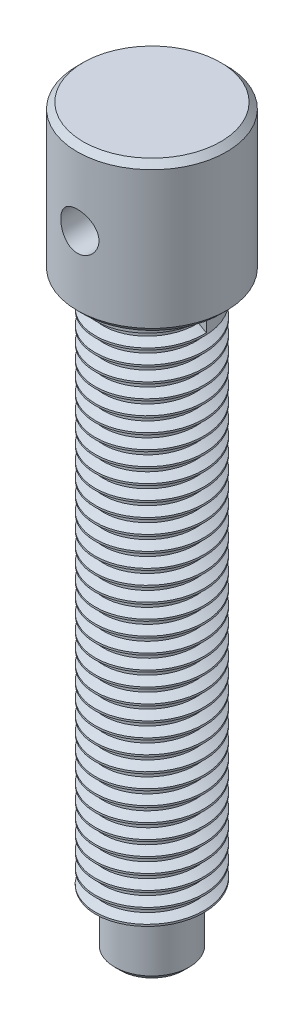
SolidWorks part; units mm, degrees
ref_plane "Front Plane" through (0, 0, 0) normal (0, 0, 1) x (1, 0, 0)
ref_plane "Top Plane" through (0, 0, 0) normal (0, 1, 0) x (1, 0, 0)
ref_plane "Right Plane" through (0, 0, 0) normal (1, 0, 0) x (0, 0, -1)
sketch "Sketch1" plane through (0, 0, 0) normal (0, 1, 0) x (1, 0, 0)
  circle A0 centre (0, 0) radius 6.35
  dimension "D1" = 12.7
extrude "Boss-Extrude1" add sketch "Sketch1" against normal blind 12.7
sketch "Sketch2" plane through (0, -12.7, 0) normal (0, -1, 0) x (1, 0, 0)
  circle A0 centre (0, 0) radius 4.625
  dimension "D1" = 9.25
extrude "Boss-Extrude2" add sketch "Sketch2" along normal blind 45
sketch "Sketch3" plane through (0, -57.7, 0) normal (0, -1, 0) x (1, 0, 0)
  circle A0 centre (0, 0) radius 3.175
  dimension "D1" = 6.35
extrude "Boss-Extrude3" add sketch "Sketch3" along normal blind 5
chamfer "Chamfer1" distance 0.5 angle 45 3 edges at (0, 0, 6.35) (0, -12.7, 6.35) (0, -62.7, -3.175)
thread "Thread1" pitch 1.25 method cut profile "Thread Profile1" start angle 0, offset 2, length 45, pitch 1.25, diameter 9.25
ref_plane "Plane1" through (4.625, -59.7, 0) normal (0, 0, 1) x (1, 0, 0)
sketch "Thread Profile1" plane through (4.625, -59.7, 0) normal (0, 0, 1) x (1, 0, 0)
  line L0 (0, 0) -> (0, 1.25) construction
  line L11 (0, 0) -> (0, 1.0937)
  line L12 (0, 1.0937) -> (-0.6766, 0.7031)
  line L13 (-0.6766, 0.7031) -> (-0.6766, 0.3906)
  line L15 (-0.6766, 0.3906) -> (0, 0)
  line L17 (-0.6766, 0.5469) -> (0, 0.5469) construction
  point P2 (0, 0)
  dimension "Pitch" = 1.25
  dimension "Profile_Angle" = 60
  dimension "Profile_Land" = 0.3125
  dimension "Profile_Height" = 0.6766
sketch "Sketch8" plane through (0, 0, 0) normal (0, 0, 1) x (1, 0, 0)
  line L0 (5.85, 0) -> (-5.85, 0) construction
  circle A0 centre (0, -6.35) radius 1.625
  point P5 (0, 0)
  dimension "D1" = 3.25
  dimension "D2" = 6.35
extrude "Cut-Extrude1" cut sketch "Sketch8" against normal through all both and the other way through all
